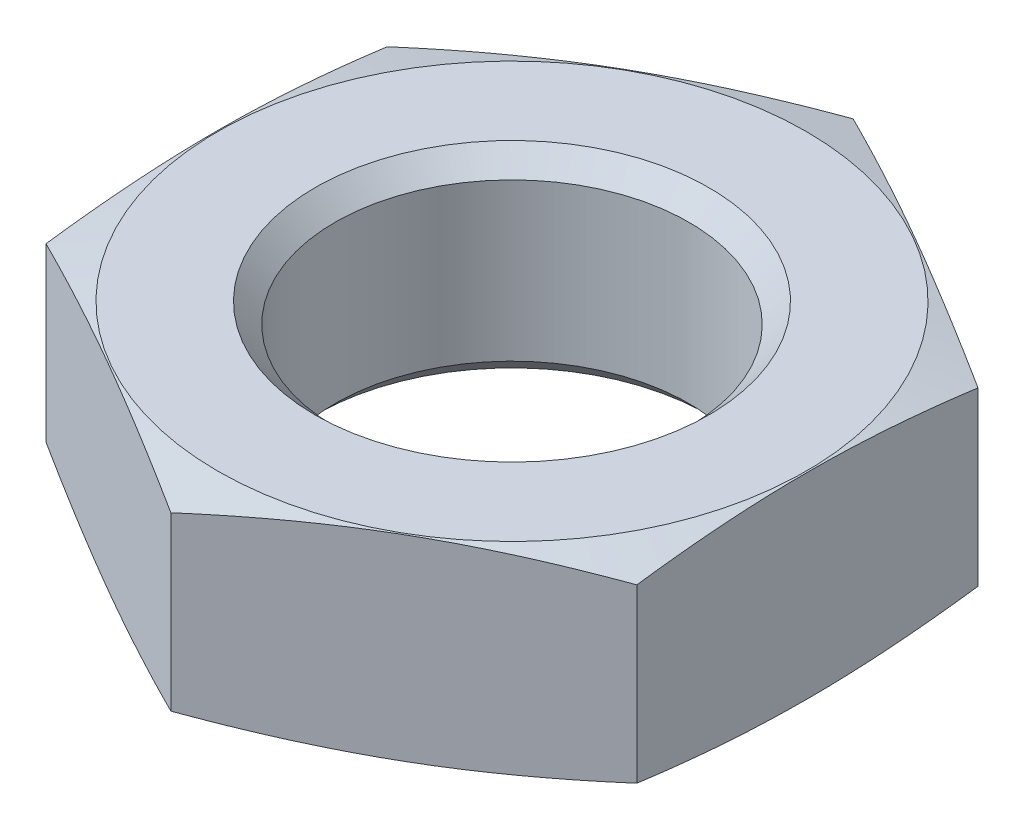
SolidWorks part; units mm, degrees
ref_plane "Front Plane" through (0, 0, 0) normal (0, 0, 1) x (1, 0, 0)
ref_plane "Top Plane" through (0, 0, 0) normal (0, 1, 0) x (1, 0, 0)
ref_plane "Right Plane" through (0, 0, 0) normal (1, 0, 0) x (0, 0, -1)
sketch "Sketch1" plane through (0, 0, 0) normal (0, 0, 1) x (1, 0, 0)
  line L0 (0, 0) -> (11.95, 0)
  line L1 (11.95, 0) -> (26.8782, -4)
  line L2 (26.8782, -4) -> (11.95, -8)
  line L3 (11.95, -8) -> (0, -8)
  line L4 (0, -8) -> (0, 0)
  line L5 (0, -8) -> (0, 0) construction
revolve "Revolve1" add sketch "Sketch1" angle 360 about L5
sketch "Sketch2" plane through (0, 0, 0) normal (0, 1, 0) x (1, 0, 0)
  line L0 (-48, 48) -> (-48, -48)
  line L1 (-48, -48) -> (48, -48)
  line L2 (48, -48) -> (48, 48)
  line L3 (48, 48) -> (-48, 48)
  line L4 (-12, -6.9282) -> (0, -13.8564)
  line L5 (0, -13.8564) -> (12, -6.9282)
  line L6 (12, -6.9282) -> (12, 6.9282)
  line L7 (12, 6.9282) -> (0, 13.8564)
  line L8 (0, 13.8564) -> (-12, 6.9282)
  line L9 (-12, 6.9282) -> (-12, -6.9282)
extrude "Cut-Extrude1" cut sketch "Sketch2" along normal blind 9 and the other way blind 9
sketch "Sketch3" plane through (0, 0, 0) normal (0, 0, 1) x (1, 0, 0)
  line L0 (0, 0) -> (8, 0)
  line L1 (8, 0) -> (7.188, -0.812)
  line L2 (7.188, -0.812) -> (7.188, -7.188)
  line L3 (7.188, -7.188) -> (8, -8)
  line L4 (8, -8) -> (0, -8)
  line L5 (0, -8) -> (0, 0)
  line L6 (0, -8) -> (0, 0) construction
revolve "Cut-Revolve1" cut sketch "Sketch3" angle 360 about L6 reverse direction yes
cosmetic thread "Cosmetic Thread1" parameters "D1"=8, "D2"=16
ref_plane "Plane1" through (0, -4, 0) normal (0, 1, 0) x (1, 0, 0)
ref_plane "2CYL XY" through (0, -4, 0) normal (0, 1, 0) x (1, 0, 0)
ref_plane "2CYL XZ" through (0, 0, 0) normal (0, 0, 1) x (1, 0, 0)
ref_plane "2CYL YZ" through (0, 0, 0) normal (1, 0, 0) x (0, 0, -1)
ref_axis "2CYL X" through (-80.9, -4, 0) along (1, 0, 0)
ref_axis "2CYL Y" through (0, -4, 50) along (0, 0, -1)
ref_axis "2CYL Z" through (0, 50, 0) along (0, -1, 0)
sketch3d "2CYL"
  point P0 (0, -4, 0)
ref_plane "din439b_punkt XY" through (0, 0, 0) normal (0, 1, 0) x (1, 0, 0)
ref_plane "din439b_punkt XZ" through (0, 0, 0) normal (0, 0, 1) x (1, 0, 0)
ref_plane "din439b_punkt YZ" through (0, 0, 0) normal (1, 0, 0) x (0, 0, -1)
ref_axis "din439b_punkt X" through (-80.9, 0, 0) along (1, 0, 0)
ref_axis "din439b_punkt Y" through (0, 0, 50) along (0, 0, -1)
ref_axis "din439b_punkt Z" through (0, 50, 0) along (0, -1, 0)
sketch3d "din439b_punkt"
  point P0 (0, 0, 0)
